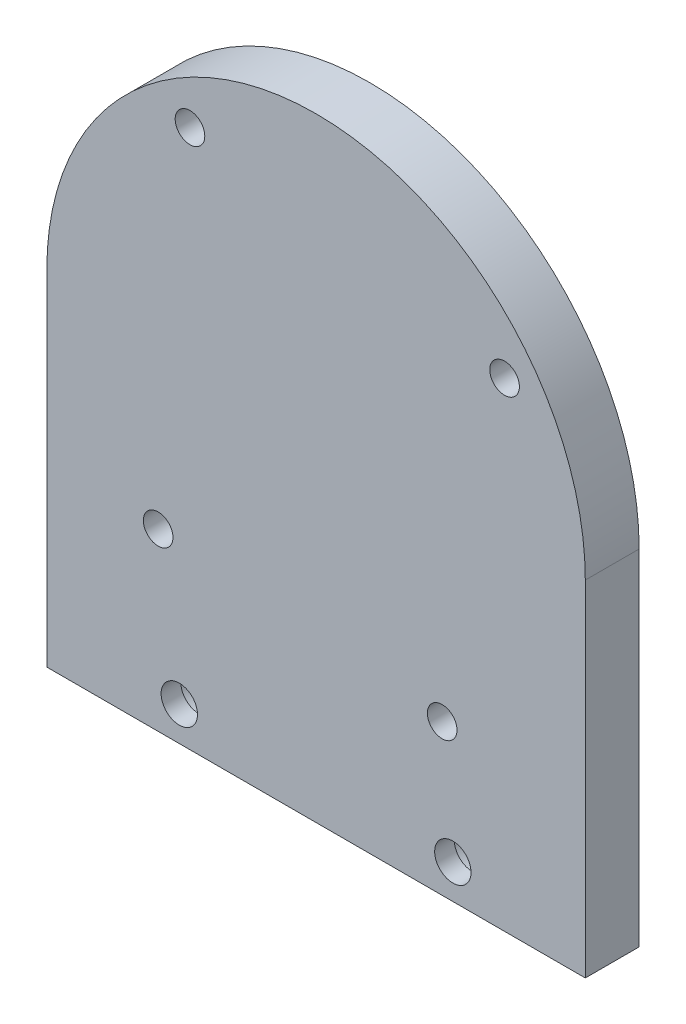
SolidWorks part; units mm, degrees
ref_plane "Front Plane" through (0, 0, 0) normal (0, 0, 1) x (1, 0, 0)
ref_plane "Top Plane" through (0, 0, 0) normal (0, 1, 0) x (1, 0, 0)
ref_plane "Right Plane" through (0, 0, 0) normal (1, 0, 0) x (0, 0, -1)
sketch "Sketch1" plane through (0, 0, 0) normal (0, 0, 1) x (1, 0, 0)
  line L1 (50, 0) -> (-50, 0)
  line L2 (50, 0) -> (50, -64)
  line L3 (50, -64) -> (-50, -64)
  line L4 (-50, 0) -> (-50, -64)
  circle A0 centre (0, 0) radius 50
  dimension "D1" = 100
  dimension "D2" = 64
extrude "Boss-Extrude1" add sketch "Sketch1" along normal blind 10 contours A0 L3 L2 | A0 L4 L3 | L1 A0 | L1 A0
ref_point "Point1"
sketch "Sketch3" plane through (0, 0, 0) normal (0, 0, -1) x (-1, 0, 0)
  line L0 (0, 43) -> (0, 0)
  line L1 (0, 0) -> (0, -43)
  circle A0 centre (0, 0) radius 43
  dimension "D1" = 86
hole_wizard "CBORE for M5 SHCS1" positions "Sketch8" profile "Sketch9" counterbore size "M5" standard "ANSI Metric" end condition up to next
sketch "Sketch8" plane through (0, 0, 0) normal (0, 0, -1) x (-1, 0, 0)
  circle A0 centre (0, 0) radius 43 construction
  point P0 (-35.007, 24.9702)
  point P7 (-23.4195, -36.0628)
  point P10 (29.3259, -31.4482)
  point P12 (23.4195, 36.0628)
  dimension "D1" = 54.5
  dimension "D2" = 33
  dimension "D3" = 33
  dimension "D4" = 43
sketch "Sketch9" plane through (35.007, 24.9702, 0) normal (1, 0, 0) x (0, 1, 0)
  line L0 (0, 0) -> (0, 10)
  line L1 (0, 10) -> (2.75, 10)
  line L3 (2.75, 10) -> (2.75, 5)
  line L4 (2.75, 5) -> (5, 5)
  line L5 (5, 5) -> (5, 0)
  line L7 (5, 0) -> (0, 0)
  line L11 (0, -6.35) -> (0, 107.95) construction
  dimension "Thru Hole Dia." = 5.5
  dimension "Thru Hole Depth" = 10
  dimension "C'Bore Dia." = 10
  dimension "C'Bore Depth" = 5
sketch "Sketch10" plane through (0, 0, 0) normal (0, 0, -1) x (-1, 0, 0)
  line L0 (0, -64) -> (0, -57.65)
  line L1 (-50, -64) -> (50, -64) construction
  line L2 (-25.4, -57.65) -> (25.4, -57.65)
  point P8 (0, -57.65)
  dimension "D1" = 50.8
  dimension "D2" = 6.35
hole_wizard "CBORE for 1/4 Socket Head Cap Screw1" positions "Sketch13" profile "Sketch14" counterbore size "1/4" standard "ANSI Inch" end condition up to next
sketch "Sketch13" plane through (0, 0, 0) normal (0, 0, -1) x (-1, 0, 0)
  point P0 (-25.4, -57.65)
  point P3 (25.4, -57.65)
sketch "Sketch14" plane through (25.4, -57.65, 0) normal (1, 0, 0) x (0, 1, 0)
  line L0 (0, 0) -> (0, 10)
  line L1 (0, 10) -> (3.3782, 10)
  line L3 (3.3782, 10) -> (3.3782, 6.35)
  line L4 (3.3782, 6.35) -> (5.5562, 6.35)
  line L5 (5.5562, 6.35) -> (5.5563, 0)
  line L7 (5.5563, 0) -> (0, 0)
  line L11 (0, -6.35) -> (0, 107.95) construction
  dimension "Thru Hole Dia." = 6.7564
  dimension "Thru Hole Depth" = 10
  dimension "C'Bore Dia." = 11.1125
  dimension "C'Bore Depth" = 6.35
sketch "Sketch15" plane through (0, -64, 0) normal (0, -1, 0) x (1, 0, 0)
  line L4 (-50, 0) -> (50, 0)
  line L5 (50, 0) -> (50, 10)
  line L6 (50, 10) -> (-50, 10)
  line L7 (-50, 10) -> (-50, 0)
  line L8 (-50, 0) -> (50, 0)
  line L9 (50, 0) -> (50, 10)
  line L10 (50, 10) -> (-50, 10)
  line L11 (-50, 10) -> (-50, 0)
  dimension "D1" = 0
